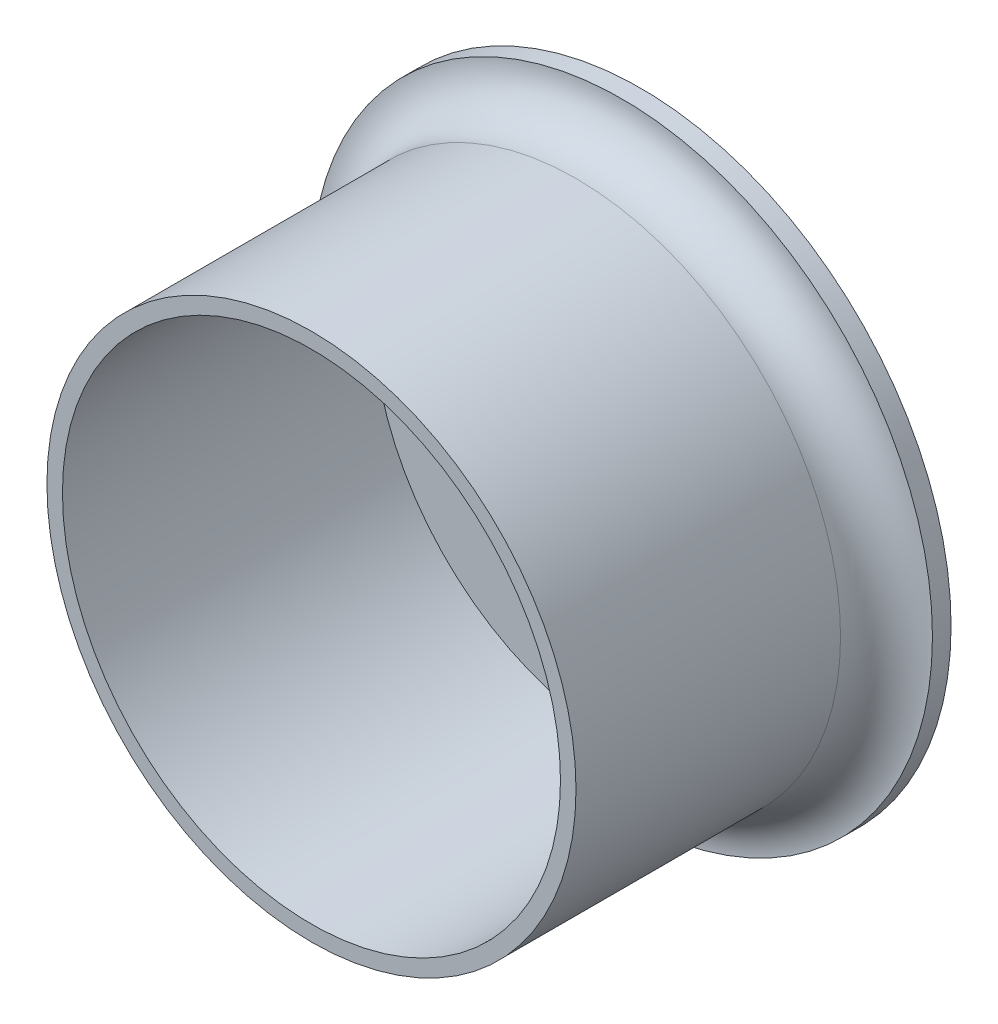
SolidWorks part; units mm, degrees
ref_plane "Front Plane" through (0, 0, 0) normal (0, 0, 1) x (1, 0, 0)
ref_plane "Top Plane" through (0, 0, 0) normal (0, 1, 0) x (1, 0, 0)
ref_plane "Right Plane" through (0, 0, 0) normal (1, 0, 0) x (0, 0, -1)
sketch "Sketch2" plane through (0, 0, 0) normal (0, 0, 1) x (1, 0, 0)
  circle A0 centre (0, 0) radius 40.1
  circle A2 centre (0, 0) radius 40.1
  circle A3 centre (0, 0) radius 42.6
  dimension "D1" = 80.2
  dimension "D2" = 2.5
extrude "Boss-Extrude2" add sketch "Sketch2" against normal blind 50 contours A3 A0 region at (-41.3951, 0, 0)
sketch "Sketch3" plane through (0, 0, -50) normal (0, 0, -1) x (-1, 0, 0)
  circle A2 centre (0, 0) radius 50
  dimension "D1" = 100
extrude "Boss-Extrude3" add sketch "Sketch3" along normal blind 3
sketch "Sketch4" plane through (0, 0, -53) normal (0, 0, -1) x (-1, 0, 0)
  circle A0 centre (0, 0) radius 15
  circle A1 centre (0, 0) radius 13
  circle A2 centre (0, 0) radius 35
  circle A3 centre (0, 0) radius 33
  circle A4 centre (0, 0) radius 25
  circle A5 centre (0, 0) radius 23
  circle A6 centre (0, 0) radius 43
  circle A7 centre (0, 0) radius 45
  dimension "D1" = 2
  dimension "D2" = 30
  dimension "D3" = 2
  dimension "D4" = 10
  dimension "D5" = 2
  dimension "D6" = 10
  dimension "D7" = 2
  dimension "D8" = 10
extrude "Cut-Extrude1" cut sketch "Sketch4" against normal blind 1 contours A2 A3 | A4 A5 | A0 A1 | A7 A6 region at (14.5757, 0, -53) region at (34.0101, 0, -53) region at (24.2929, 0, -53) region at (43.7272, 0, -53)
fillet "Fillet1" radius 1 8 edges at (-15, 0, -52) (-13, 0, -52) (-23, 0, -52) (-25, 0, -52) (-33, 0, -52) (-35, 0, -52) (-45, 0, -52) (-43, 0, -52)
fillet "Fillet2" radius 7.4 1 edges at (42.6, 0, -50)
